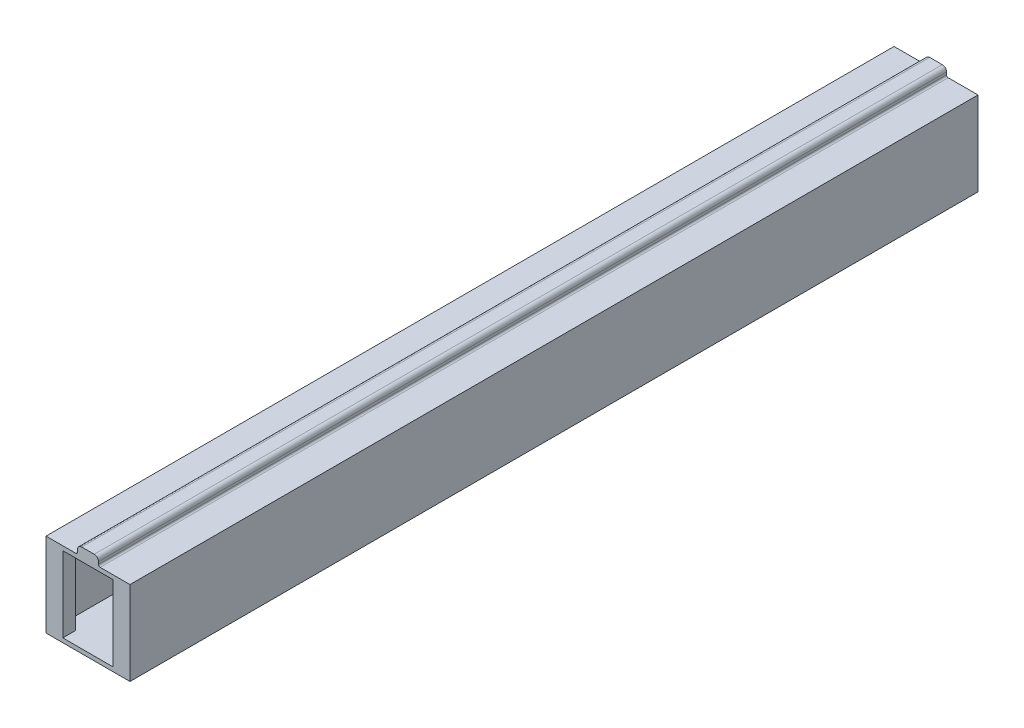
SolidWorks part; units mm, degrees
ref_plane "Front Plane" through (0, 0, 0) normal (0, 0, 1) x (1, 0, 0)
ref_plane "Top Plane" through (0, 0, 0) normal (0, 1, 0) x (1, 0, 0)
ref_plane "Right Plane" through (0, 0, 0) normal (1, 0, 0) x (0, 0, -1)
sketch "Sketch1" plane through (0, 0, 0) normal (0, 0, 1) x (1, 0, 0)
  line L0 (0, 14.5892) -> (0, -5.317) construction
  line L1 (-12.7, -12.7) -> (12.7, -12.7)
  line L2 (12.7, -12.7) -> (12.7, 12.7)
  line L3 (12.7, 12.7) -> (3.175, 12.7)
  line L4 (3.175, 12.7) -> (3.175, 15.24)
  line L5 (3.175, 15.24) -> (-3.175, 15.24)
  line L6 (-12.7, -12.7) -> (-12.7, 12.7)
  line L7 (-3.175, 12.7) -> (-3.175, 15.24)
  line L8 (-12.7, 12.7) -> (-3.175, 12.7)
  circle A0 centre (0, 0) radius 6.35 construction
  circle A1 centre (0, 0) radius 12.7 construction
  circle A2 centre (0, 0) radius 9.525 construction
  circle A3 centre (0, -9.525) radius 1.778
  circle A4 centre (-8.2489, 4.7625) radius 1.778
  circle A5 centre (8.2489, 4.7625) radius 1.778
  circle A6 centre (0, 0) radius 6.35
  point P13 (0, 0)
  point P20 (0, 0)
  point P22 (0, -12.7)
  point P25 (0, 15.24)
  dimension "D1" = 12.7
  dimension "D2" = 25.4
  dimension "D3" = 19.05
  dimension "D4" = 3.556
  dimension "D6" = 9.525
  dimension "D7" = 25.4
  dimension "D8" = 12.7
  dimension "D9" = 12.7
  dimension "D10" = 2.54
  dimension "D5" = 3
extrude "Boss-Extrude1" add sketch "Sketch1" along normal blind 2.54
sketch "Sketch2" plane through (0, 0, 2.54) normal (0, 0, 1) x (1, 0, 0)
  line L0 (-11.43, 11.43) -> (-11.43, -11.43)
  line L1 (-11.43, -11.43) -> (11.43, -11.43)
  line L2 (11.43, -11.43) -> (11.43, 11.43)
  line L3 (11.43, 11.43) -> (-11.43, 11.43)
  line L4 (-12.7, 12.7) -> (-12.7, -12.7) construction
  line L6 (-12.7, -12.7) -> (12.7, -12.7) construction
  line L7 (12.7, -12.7) -> (12.7, 12.7) construction
  line L8 (12.7, 12.7) -> (3.175, 12.7) construction
  line L9 (3.175, 12.7) -> (3.175, 15.24) construction
  line L10 (3.175, 15.24) -> (-3.175, 15.24) construction
  line L11 (-3.175, 15.24) -> (-3.175, 12.7) construction
  line L12 (-3.175, 12.7) -> (-12.7, 12.7) construction
  line L13 (-12.7, -12.7) -> (12.7, -12.7)
  line L14 (12.7, -12.7) -> (12.7, 12.7)
  line L15 (12.7, 12.7) -> (3.175, 12.7)
  line L16 (3.175, 12.7) -> (3.175, 15.24)
  line L17 (3.175, 15.24) -> (-3.175, 15.24)
  line L18 (-3.175, 15.24) -> (-3.175, 12.7)
  line L19 (-3.175, 12.7) -> (-12.7, 12.7)
  line L20 (-12.7, 12.7) -> (-12.7, -12.7)
  dimension "D1" = 22.86
  dimension "D2" = 22.86
  dimension "D3" = 1.27
  dimension "D4" = 1.27
extrude "Boss-Extrude2" add sketch "Sketch2" along normal blind 254
sketch "Sketch3" plane through (-11.43, 0, 0) normal (1, 0, 0) x (0, 0, -1)
  line L0 (-256.54, 11.43) -> (-256.54, -11.43) construction
  line L1 (-256.54, 11.43) -> (-252.73, 11.43)
  line L2 (-256.54, 11.43) -> (-256.54, -11.43)
  line L3 (-256.54, -11.43) -> (-252.73, -11.43)
  line L4 (-252.73, 11.43) -> (-252.73, -11.43)
  line L5 (-256.54, 11.43) -> (-2.54, 11.43) construction
  dimension "D1" = 22.86
  dimension "D2" = 3.81
extrude "Boss-Extrude3" add sketch "Sketch3" along normal blind 3.81
sketch "Sketch4" plane through (11.43, 0, 0) normal (-1, 0, 0) x (0, 0, 1)
  line L0 (256.54, 11.43) -> (256.54, -11.43)
  line L1 (256.54, 12.7) -> (256.54, -12.7) construction
  line L2 (256.54, -11.43) -> (251.46, -11.43)
  line L3 (251.46, -11.43) -> (251.46, 11.43)
  line L5 (251.46, 11.43) -> (256.54, 11.43)
  line L6 (256.54, -12.7) -> (0, -12.7) construction
  dimension "D1" = 22.86
  dimension "D2" = 5.08
  dimension "D3" = 1.27
extrude "Boss-Extrude4" add sketch "Sketch4" along normal blind 3.81
fillet "Fillet1" radius 1.27 2 edges at (3.175, 15.24, 128.27) (-3.175, 15.24, 128.27)
fillet "Fillet2" radius 0.508 2 edges at (3.175, 12.7, 128.27) (-3.175, 12.7, 128.27)
